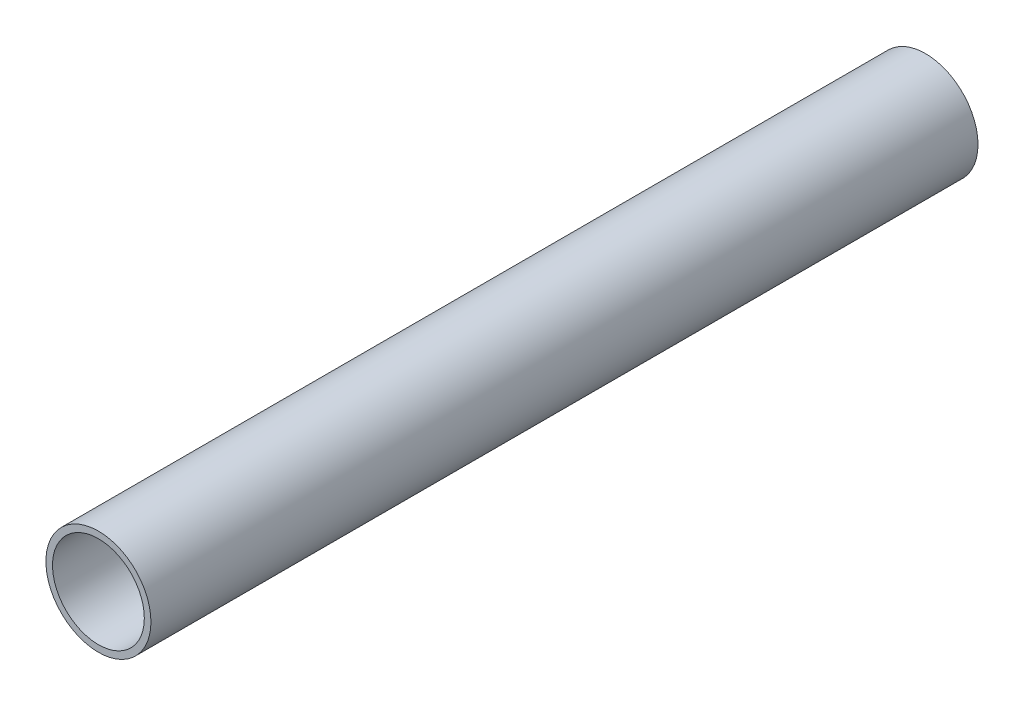
SolidWorks part; units mm, degrees
ref_plane "Front Plane" through (0, 0, 0) normal (1, 0, 0) x (0, 1, 0)
ref_plane "Top Plane" through (0, 0, 0) normal (0, 0, 1) x (0, 1, 0)
ref_plane "Right Plane" through (0, 0, 0) normal (0, 1, 0) x (-1, 0, 0)
sketch "Sketch1" plane through (0, 0, 0) normal (0, 0, 1) x (0, 1, 0)
  circle A0 centre (0, 0) radius 12.7
  circle A1 centre (0, 0) radius 11.1
  dimension "D1" = 25.4
  dimension "D2" = 22.2
extrude "Boss-Extrude1" add sketch "Sketch1" along normal blind 200
equation "\"OD\" = 1in"
equation "\"ID\" = 22.2"
equation "\"D1@Sketch1\"=\"OD\""
equation "\"D2@Sketch1\"=\"ID\""
equation "\"L\"= 200"
equation "\"D1@Boss-Extrude1\"=\"L\""
